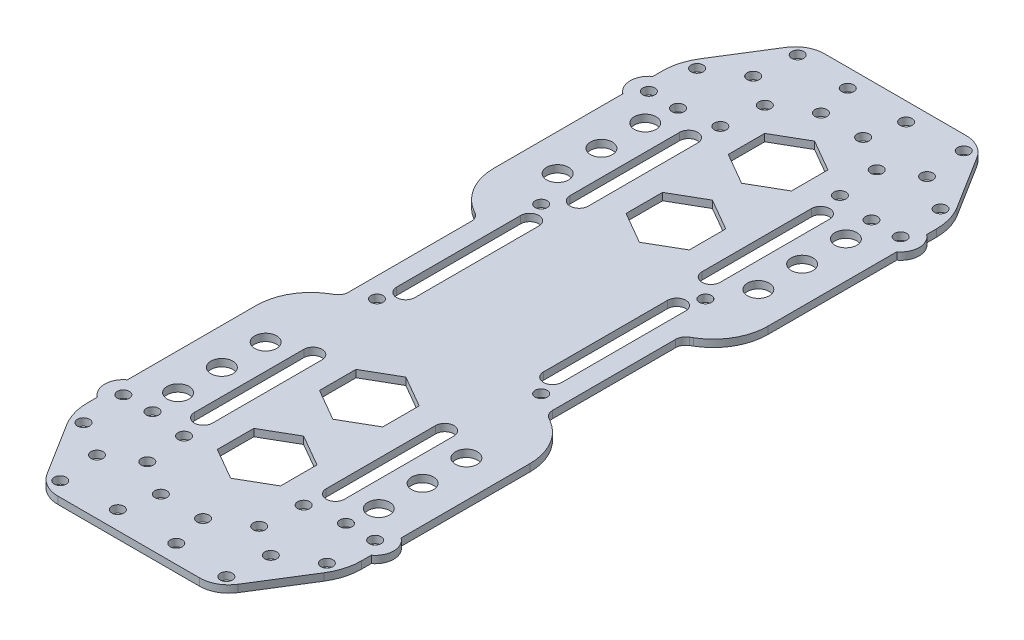
SolidWorks part; units mm, degrees
ref_plane "Front Plane" through (0, 0, 0) normal (0, 0, 1) x (1, 0, 0)
ref_plane "Top Plane" through (0, 0, 0) normal (0, 1, 0) x (1, 0, 0)
ref_plane "Right Plane" through (0, 0, 0) normal (1, 0, 0) x (0, 0, -1)
sketch "Sketch1" plane through (0, 0, 0) normal (0, 1, 0) x (1, 0, 0)
  line L0 (37.5251, 78.755) -> (37.5251, 32.6348)
  line L2 (-200, -200) -> (200, -200) construction
  line L7 (-200, -200) -> (-200, 200) construction
  line L11 (200, -200) -> (200, 200) construction
  line L14 (-200, -200) -> (200, 200) construction
  line L17 (0, 0) -> (60, 0) construction
  line L23 (0, 120) -> (0, -120) construction
  line L24 (0, 0) -> (-60, 0) construction
  line L69 (29.4047, 19.2862) -> (30.0251, 19.6444)
  line L70 (-30, -19.6299) -> (-29.4047, -19.2862)
  line L71 (-28, -16.8532) -> (-28, 16.8532)
  line L73 (37.5251, -32.6348) -> (37.5251, -78.755)
  line L74 (-29.4047, 19.2862) -> (-30, 19.6299)
  line L78 (28, -16.8532) -> (28, 16.8532)
  line L79 (30.0251, -19.6444) -> (29.4047, -19.2862)
  line L80 (-37.5, -32.6203) -> (-37.5, -78.7951)
  line L81 (-60, 36.9504) -> (-67.2154, 32.7846) [skipped]
  line L82 (-92, 0) -> (-92, -18.4752) [skipped]
  line L83 (-76, -27.7128) -> (-60, -36.9504) [skipped]
  line L84 (-200, 200) -> (200, -200) construction
  line L85 (-200, 200) -> (200, 200) construction
  line L86 (-22.7528, 101.0355) -> (-33.3512, 84.0745) construction
  line L87 (-28.052, 92.555) -> (-200, 200) construction
  line L88 (-33.3512, 84.0745) -> (-16.3903, 73.4761) construction
  line L89 (-16.3903, 73.4761) -> (-5.7919, 90.4371) construction
  line L90 (16.3903, 73.4761) -> (5.7919, 90.4371) construction
  line L91 (-19.3786, 105) -> (19.3786, 105)
  line L92 (-35.2207, 86.7439) -> (-26.163, 101.2394)
  line L93 (35.2458, 86.7038) -> (26.163, 101.2394)
  line L94 (-37.5, 78.7951) -> (-37.5, 32.6203)
  line L95 (35.2458, -86.7038) -> (26.163, -101.2394)
  line L96 (-19.3786, -105) -> (19.3786, -105)
  line L97 (-35.2207, -86.7439) -> (-26.163, -101.2394)
  line L98 (33.3512, 84.0745) -> (16.3903, 73.4761) construction
  line L99 (22.7528, 101.0355) -> (33.3512, 84.0745) construction
  line L100 (22.7528, -101.0355) -> (33.3512, -84.0745) construction
  line L101 (33.3512, -84.0745) -> (16.3903, -73.4761) construction
  line L102 (16.3903, -73.4761) -> (5.7919, -90.4371) construction
  line L103 (-16.3903, -73.4761) -> (-5.7919, -90.4371) construction
  line L104 (-33.3512, -84.0745) -> (-16.3903, -73.4761) construction
  line L105 (-22.7528, -101.0355) -> (-33.3512, -84.0745) construction
  circle A7 centre (200, 200) radius 177.8 construction
  circle A8 centre (-200, 200) radius 177.8 construction
  circle A9 centre (-200, -200) radius 177.8 construction
  circle A10 centre (200, -200) radius 177.8 construction
  circle A29 centre (-27.4977, 64) radius 3
  circle A30 centre (-27.4989, 52) radius 3
  circle A31 centre (-27.5, 40) radius 3
  circle A70 centre (27.5, 40) radius 3
  circle A71 centre (27.4989, 52) radius 3
  circle A72 centre (27.4977, 64) radius 3
  circle A73 centre (27.4977, -64) radius 3
  circle A74 centre (27.4989, -52) radius 3
  circle A75 centre (27.5, -40) radius 3
  circle A76 centre (-27.5, -40) radius 3
  circle A77 centre (-27.4989, -52) radius 3
  circle A78 centre (-27.4977, -64) radius 3
  circle A79 centre (-34.4977, 72) radius 1.65
  circle A80 centre (34.4977, 72) radius 1.65
  circle A82 centre (-34.4977, -72) radius 1.65
  circle A84 centre (-22.7528, 101.0355) radius 1.65
  circle A92 centre (22.7528, 101.0355) radius 3 construction
  circle A94 centre (5.7919, 90.4371) radius 3 construction
  circle A96 centre (16.3903, 73.4761) radius 3 construction
  circle A97 centre (33.3512, 84.0745) radius 3 construction
  circle A100 centre (33.3512, -84.0745) radius 3 construction
  circle A102 centre (16.3903, -73.4761) radius 3 construction
  circle A104 centre (22.7528, -101.0355) radius 3 construction
  circle A106 centre (5.7919, -90.4371) radius 3 construction
  circle A108 centre (-5.7919, -90.4371) radius 3 construction
  circle A110 centre (-16.3903, -73.4761) radius 3 construction
  circle A111 centre (-33.3512, -84.0745) radius 3 construction
  circle A114 centre (-22.7528, -101.0355) radius 3 construction
  arc A115 (26.163, 101.2394) -> (19.3786, 105) centre (19.3786, 97) ccw
  arc A116 (-19.3786, 105) -> (-26.163, 101.2394) centre (-19.3786, 97) ccw
  arc A117 (35.2458, 86.7038) -> (37.5251, 78.755) centre (22.5251, 78.755) cw
  arc A118 (-35.2207, 86.7439) -> (-37.5, 78.7951) centre (-22.5, 78.7951) ccw
  arc A119 (35.2458, -86.7038) -> (37.5251, -78.755) centre (22.5251, -78.755) ccw
  arc A120 (26.163, -101.2394) -> (19.3786, -105) centre (19.3786, -97) cw
  arc A121 (-19.3786, -105) -> (-26.163, -101.2394) centre (-19.3786, -97) cw
  arc A122 (-35.2207, -86.7439) -> (-37.5, -78.7951) centre (-22.5, -78.7951) cw
  arc A123 (-30, 19.6299) -> (-37.5, 32.6203) centre (-22.5, 32.6203) cw
  arc A124 (30.0251, 19.6444) -> (37.5251, 32.6348) centre (22.5251, 32.6348) ccw
  arc A125 (37.5251, -32.6348) -> (30.0251, -19.6444) centre (22.5251, -32.6348) ccw
  arc A126 (-30, -19.6299) -> (-37.5, -32.6203) centre (-22.5, -32.6203) ccw
  arc A127 (-28, 16.8532) -> (-29.4047, 19.2862) centre (-30.8094, 16.8532) ccw
  arc A128 (29.4047, 19.2862) -> (28, 16.8532) centre (30.8094, 16.8532) ccw
  arc A129 (28, -16.8532) -> (29.4047, -19.2862) centre (30.8094, -16.8532) ccw
  arc A130 (-29.4047, -19.2862) -> (-28, -16.8532) centre (-30.8094, -16.8532) ccw
  circle A131 centre (-33.3512, 84.0745) radius 1.65
  circle A132 centre (-5.7919, 90.4371) radius 1.65
  circle A133 centre (-16.3903, 73.4761) radius 1.65
  circle A134 centre (16.3903, 73.4761) radius 1.65
  circle A135 centre (5.7919, 90.4371) radius 1.65
  circle A136 centre (33.3512, 84.0745) radius 1.65
  circle A137 centre (22.7528, 101.0355) radius 1.65
  circle A138 centre (-16.3903, -73.4761) radius 1.65
  circle A139 centre (16.3903, -73.4761) radius 1.65
  circle A140 centre (33.3512, -84.0745) radius 3 construction
  circle A141 centre (5.7919, -90.4371) radius 3 construction
  circle A142 centre (22.7528, -101.0355) radius 3 construction
  circle A143 centre (22.7528, -101.0355) radius 1.65
  circle A144 centre (33.3512, -84.0745) radius 1.65
  circle A145 centre (5.7919, -90.4371) radius 1.65
  circle A146 centre (-5.7919, -90.4371) radius 1.65
  circle A147 centre (-33.3512, -84.0745) radius 1.65
  circle A148 centre (-22.7528, -101.0355) radius 1.65
  circle A149 centre (34.4977, -72) radius 1.65
  point P22 (0, 0)
  point P26 (-200, 200)
  point P54 (0, 0)
  point P151 (-28, 18.4752)
  point P154 (28, 18.4752)
  point P157 (28, -18.4752)
  point P160 (-28, -18.4752)
  dimension "D4" = 60
  dimension "D5" = 400
  dimension "D7" = 15
  dimension "D8" = 15
  dimension "D9" = 355.6
  dimension "D10" = 8
  dimension "D11" = 40
  dimension "D13" = 3.3
  dimension "D14" = 10
  dimension "D15" = 3.3
  dimension "D16" = 20
  dimension "D17" = 32
  dimension "D18" = 90
  dimension "D19" = 105
  dimension "D20" = 3.3
  dimension "D21" = 20
  dimension "D22" = 8
  dimension "D23" = 6
  dimension "D24" = 2.8094
  dimension "D25" = 90
  dimension "D26" = 90
  dimension "D27" = 12
  dimension "D28" = 12
  dimension "D29" = 20
  dimension "D6" = 60
  dimension "D12" = 7
  dimension "D3" = 400
extrude "Boss-Extrude1" add sketch "Sketch1" along normal blind 2
sketch "Sketch2" plane through (0, 2, 0) normal (0, 1, 0) x (1, 0, 0)
  line L33 (28, -16.8532) -> (28, 16.8532) construction
  line L36 (28, 0) -> (-28, 0) construction
  line L49 (-28, 16.8532) -> (-28, -16.8532) construction
  circle A11 centre (-34.4977, 72) radius 5.0909
  circle A12 centre (34.4977, 72) radius 5.0909
  circle A13 centre (34.4977, -72) radius 5.0909
  circle A14 centre (-34.4977, -72) radius 5.0909
  circle A15 centre (-34.4977, 72) radius 1.65
  circle A16 centre (34.4977, 72) radius 1.65
  circle A17 centre (34.4977, -72) radius 1.65
  circle A18 centre (-34.4977, -72) radius 1.65
extrude "Boss-Extrude2" add sketch "Sketch2" against normal up to surface (2 mm away) up to face at (-22.7528, 0, 99.3855)
sketch "Sketch3" plane through (0, 2, 0) normal (0, 1, 0) x (1, 0, 0)
  line L4 (-28, 0) -> (28, 0) construction
  line L5 (-28, 16.8532) -> (-28, -16.8532) construction
  line L6 (28, -16.8532) -> (28, 16.8532) construction
  line L31 (0, 82.9095) -> (-8.6603, 77.9095)
  line L38 (-8.6603, 77.9095) -> (-8.6603, 67.9095)
  line L39 (-8.6603, 67.9095) -> (0, 62.9095)
  line L40 (0, 62.9095) -> (8.6603, 67.9095)
  line L41 (8.6603, 67.9095) -> (8.6603, 77.9095)
  line L42 (8.6603, 77.9095) -> (0, 82.9095)
  line L43 (0, 54.9095) -> (-8.6603, 49.9095)
  line L44 (-8.6603, 49.9095) -> (-8.6603, 39.9095)
  line L45 (-8.6603, 39.9095) -> (0, 34.9095)
  line L46 (0, 34.9095) -> (8.6603, 39.9095)
  line L47 (8.6603, 39.9095) -> (8.6603, 49.9095)
  line L48 (8.6603, 49.9095) -> (0, 54.9095)
  line L49 (0, 26.9095) -> (-8.6603, 21.9095)
  line L50 (-8.6603, 21.9095) -> (-8.6603, 11.9095)
  line L51 (-8.6603, 11.9095) -> (0, 6.9095)
  line L52 (0, 6.9095) -> (8.6603, 11.9095)
  line L53 (8.6603, 11.9095) -> (8.6603, 21.9095)
  line L54 (8.6603, 21.9095) -> (0, 26.9095)
  line L55 (0, -1.0905) -> (-8.6603, -6.0905)
  line L56 (-8.6603, -6.0905) -> (-8.6603, -16.0905)
  line L57 (-8.6603, -16.0905) -> (0, -21.0905)
  line L58 (0, -21.0905) -> (8.6603, -16.0905)
  line L59 (8.6603, -16.0905) -> (8.6603, -6.0905)
  line L60 (8.6603, -6.0905) -> (0, -1.0905)
  line L61 (0, -29.0905) -> (-8.6603, -34.0905)
  line L62 (-8.6603, -34.0905) -> (-8.6603, -44.0905)
  line L63 (-8.6603, -44.0905) -> (0, -49.0905)
  line L64 (0, -49.0905) -> (8.6603, -44.0905)
  line L65 (8.6603, -44.0905) -> (8.6603, -34.0905)
  line L66 (8.6603, -34.0905) -> (0, -29.0905)
  line L67 (0, -57.0905) -> (-8.6603, -62.0905)
  line L68 (-8.6603, -62.0905) -> (-8.6603, -72.0905)
  line L69 (-8.6603, -72.0905) -> (0, -77.0905)
  line L70 (0, -77.0905) -> (8.6603, -72.0905)
  line L71 (8.6603, -72.0905) -> (8.6603, -62.0905)
  line L72 (8.6603, -62.0905) -> (0, -57.0905)
  circle A3 centre (-32.5, 28) radius 1.5
  circle A8 centre (32.5, 28) radius 1.5
  circle A12 centre (0, 72.9095) radius 8.6603 construction
  circle A13 centre (0, 44.9095) radius 8.6603 construction
  circle A24 centre (0, 16.9095) radius 8.6603 construction
  circle A25 centre (0, -11.0905) radius 8.6603 construction
  circle A26 centre (0, -39.0905) radius 8.6603 construction
  circle A27 centre (0, -67.0905) radius 8.6603 construction
  circle A39 centre (32.5, -28) radius 1.5
  circle A50 centre (-32.5, -28) radius 1.5
sketch "Sketch5" plane through (0, 2, 0) normal (0, 1, 0) x (1, 0, 0)
  line L0 (-19.3786, 105) -> (19.3786, 105) construction
  line L1 (0, 120) -> (0, -120) construction
  line L2 (0, 105) -> (0, -105) construction
  line L3 (-19.3786, -105) -> (19.3786, -105) construction
  line L4 (-18.0747, 66.4819) -> (-18.0747, 36.4819) construction
  line L5 (-60, 0) -> (60, 0) construction
  line L6 (-15.5747, 66.4819) -> (-15.5747, 36.4819)
  line L8 (-25.75, -34) -> (25.25, -34) construction
  line L9 (-25.75, -34) -> (-25.75, 34) construction
  line L10 (-25.75, 34) -> (25.25, 34) construction
  line L11 (25.25, -34) -> (25.25, 34) construction
  line L12 (-22.5, 30.5) -> (-22.5, -14.5) construction
  line L13 (-24.15, 30.5) -> (-25.75, 30.5) construction
  line L21 (-22.5, 30.5) -> (22.5, 30.5) construction
  line L22 (22.5, 30.5) -> (22.5, -14.5) construction
  line L23 (-20.5747, 66.4819) -> (-20.5747, 36.4819)
  line L24 (-20.1305, 25) -> (-20.1305, 8) construction
  line L25 (-20.1305, 8) -> (-20.1305, -9) construction
  line L26 (-20.1305, 25) -> (-20.1305, -9) construction
  line L27 (-17.6305, 25) -> (-17.6305, -9)
  line L28 (-22.6305, 25) -> (-22.6305, -9)
  line L29 (20.1305, 25) -> (20.1305, -9) construction
  line L30 (17.6305, 25) -> (17.6305, -9)
  line L31 (22.6305, 25) -> (22.6305, -9)
  line L32 (18.0747, 66.4819) -> (18.0747, 36.4819) construction
  line L33 (15.5747, 66.4819) -> (15.5747, 36.4819)
  line L34 (20.5747, 66.4819) -> (20.5747, 36.4819)
  line L35 (18.0747, -66.4819) -> (18.0747, -36.4819) construction
  line L36 (15.5747, -66.4819) -> (15.5747, -36.4819)
  line L37 (20.5747, -66.4819) -> (20.5747, -36.4819)
  line L38 (-18.0747, -66.4819) -> (-18.0747, -36.4819) construction
  line L39 (-15.5747, -66.4819) -> (-15.5747, -36.4819)
  line L40 (-20.5747, -66.4819) -> (-20.5747, -36.4819)
  line L42 (8.6603, 49.9095) -> (0, 54.9095)
  line L43 (0, 54.9095) -> (-8.6603, 49.9095)
  line L44 (-8.6603, 49.9095) -> (-8.6603, 39.9095)
  line L45 (-8.6603, 39.9095) -> (0, 34.9095)
  line L46 (0, 34.9095) -> (8.6603, 39.9095)
  line L47 (8.6603, 39.9095) -> (8.6603, 49.9095)
  line L48 (8.6603, -44.0905) -> (8.6603, -34.0905)
  line L49 (8.6603, -34.0905) -> (0, -29.0905)
  line L50 (0, -29.0905) -> (-8.6603, -34.0905)
  line L51 (-8.6603, -34.0905) -> (-8.6603, -44.0905)
  line L52 (-8.6603, -44.0905) -> (0, -49.0905)
  line L53 (0, -49.0905) -> (8.6603, -44.0905)
  line L54 (0, 62.9095) -> (8.6603, 67.9095)
  line L55 (8.6603, 67.9095) -> (8.6603, 77.9095)
  line L56 (8.6603, 77.9095) -> (0, 82.9095)
  line L57 (0, 82.9095) -> (-8.6603, 77.9095)
  line L58 (-8.6603, 77.9095) -> (-8.6603, 67.9095)
  line L59 (-8.6603, 67.9095) -> (0, 62.9095)
  line L60 (8.6603, -62.0905) -> (0, -57.0905)
  line L61 (0, -57.0905) -> (-8.6603, -62.0905)
  line L62 (-8.6603, -62.0905) -> (-8.6603, -72.0905)
  line L63 (-8.6603, -72.0905) -> (0, -77.0905)
  line L64 (0, -77.0905) -> (8.6603, -72.0905)
  line L65 (8.6603, -72.0905) -> (8.6603, -62.0905)
  circle A0 centre (-26.4977, 72) radius 1.65
  circle A1 centre (-34.4977, 72) radius 1.65 construction
  circle A2 centre (-34.4977, 72) radius 3.5 construction
  circle A3 centre (-8, 100) radius 1.65
  circle A5 centre (8, 100) radius 1.65
  circle A6 centre (26.4977, 72) radius 1.65
  circle A7 centre (26.4977, -72) radius 1.65
  circle A8 centre (8, -100) radius 1.65
  circle A9 centre (-8, -100) radius 1.65
  circle A10 centre (-26.4977, -72) radius 1.65
  circle A12 centre (-22.5, 30.5) radius 1.65
  circle A13 centre (22.5, 30.5) radius 1.65
  circle A14 centre (-22.5, -14.5) radius 1.65
  circle A15 centre (22.5, -14.5) radius 1.65
  arc A16 (-15.5747, 66.4819) -> (-20.5747, 66.4819) centre (-18.0747, 66.4819) ccw
  arc A17 (-20.5747, 36.4819) -> (-15.5747, 36.4819) centre (-18.0747, 36.4819) ccw
  arc A18 (-17.6305, 25) -> (-22.6305, 25) centre (-20.1305, 25) ccw
  arc A19 (-22.6305, -9) -> (-17.6305, -9) centre (-20.1305, -9) ccw
  arc A20 (17.6305, 25) -> (22.6305, 25) centre (20.1305, 25) cw
  arc A21 (22.6305, -9) -> (17.6305, -9) centre (20.1305, -9) cw
  arc A22 (15.5747, 66.4819) -> (20.5747, 66.4819) centre (18.0747, 66.4819) cw
  arc A23 (20.5747, 36.4819) -> (15.5747, 36.4819) centre (18.0747, 36.4819) cw
  arc A24 (15.5747, -66.4819) -> (20.5747, -66.4819) centre (18.0747, -66.4819) ccw
  arc A25 (20.5747, -36.4819) -> (15.5747, -36.4819) centre (18.0747, -36.4819) ccw
  arc A26 (-15.5747, -66.4819) -> (-20.5747, -66.4819) centre (-18.0747, -66.4819) cw
  arc A27 (-20.5747, -36.4819) -> (-15.5747, -36.4819) centre (-18.0747, -36.4819) cw
  circle A28 centre (0, 44.9095) radius 8.6603 construction
  circle A29 centre (0, -39.0905) radius 8.6603 construction
  circle A30 centre (0, 72.9095) radius 8.6603 construction
  circle A31 centre (0, -67.0905) radius 8.6603 construction
  point P38 (0, 0)
  point P52 (-18.0747, 51.4819)
  point P59 (-20.1305, 8)
  point P67 (20.1305, 8)
  point P74 (18.0747, 51.4819)
  point P81 (18.0747, -51.4819)
  point P88 (-18.0747, -51.4819)
  dimension "D2" = 3.3
  dimension "D3" = 8
  dimension "D4" = 5
  dimension "D5" = 3.3
  dimension "D6" = 8
  dimension "D9" = 6.5
  dimension "D10" = 3.3
  dimension "D12" = 22.5
  dimension "D13" = 45
  dimension "D15" = 17
  dimension "D1" = 8
  dimension "D7" = 68
  dimension "D8" = 51
  dimension "D11" = 45
  dimension "D14" = 45
  dimension "D16" = 17
extrude "Cut-Extrude1" cut sketch "Sketch5" against normal blind 2
sketch "Sketch6" plane through (0, 2, 0) normal (0, 1, 0) x (1, 0, 0)
  line L0 (-33.3512, -84.0745) -> (-22.7528, -101.0355) construction
  line L1 (-22.7528, -101.0355) -> (-5.7919, -90.4371) construction
  line L2 (-5.7919, -90.4371) -> (-16.3903, -73.4761) construction
  line L3 (-16.3903, -73.4761) -> (-33.3512, -84.0745) construction
  line L4 (-28.052, -92.555) -> (-19.5716, -87.2558) construction
  line L5 (-19.5716, -87.2558) -> (-11.0911, -81.9566) construction
  line L6 (22.7528, -101.0355) -> (33.3512, -84.0745) construction
  line L7 (33.3512, -84.0745) -> (16.3903, -73.4761) construction
  line L8 (16.3903, -73.4761) -> (5.7919, -90.4371) construction
  line L9 (0, 105) -> (0, -105) construction
  line L10 (28.052, -92.555) -> (19.5716, -87.2558) construction
  line L11 (5.7919, -90.4371) -> (22.7528, -101.0355) construction
  line L12 (11.0911, -81.9566) -> (19.5716, -87.2558) construction
  line L13 (19.3786, 105) -> (-19.3786, 105) construction
  line L14 (-19.3786, -105) -> (19.3786, -105) construction
  line L15 (0, 0) -> (41.3874, 0) construction
  line L16 (11.0911, 81.9566) -> (19.5716, 87.2558) construction
  line L17 (5.7919, 90.4371) -> (22.7528, 101.0355) construction
  line L18 (28.052, 92.555) -> (19.5716, 87.2558) construction
  line L19 (16.3903, 73.4761) -> (5.7919, 90.4371) construction
  line L20 (33.3512, 84.0745) -> (16.3903, 73.4761) construction
  line L21 (22.7528, 101.0355) -> (33.3512, 84.0745) construction
  line L22 (-19.5716, 87.2558) -> (-11.0911, 81.9566) construction
  line L23 (-28.052, 92.555) -> (-19.5716, 87.2558) construction
  line L24 (-16.3903, 73.4761) -> (-33.3512, 84.0745) construction
  line L25 (-5.7919, 90.4371) -> (-16.3903, 73.4761) construction
  line L26 (-22.7528, 101.0355) -> (-5.7919, 90.4371) construction
  line L27 (-33.3512, 84.0745) -> (-22.7528, 101.0355) construction
  circle A0 centre (-15.3313, -84.6062) radius 1.65
  circle A1 centre (-23.8118, -89.9054) radius 1.65
  circle A2 centre (23.8118, -89.9054) radius 1.65
  circle A3 centre (15.3313, -84.6062) radius 1.65
  circle A4 centre (15.3313, 84.6062) radius 1.65
  circle A5 centre (23.8118, 89.9054) radius 1.65
  circle A6 centre (-23.8118, 89.9054) radius 1.65
  circle A7 centre (-15.3313, 84.6062) radius 1.65
  dimension "D1" = 3.3
extrude "Cut-Extrude2" cut sketch "Sketch6" against normal blind 10
